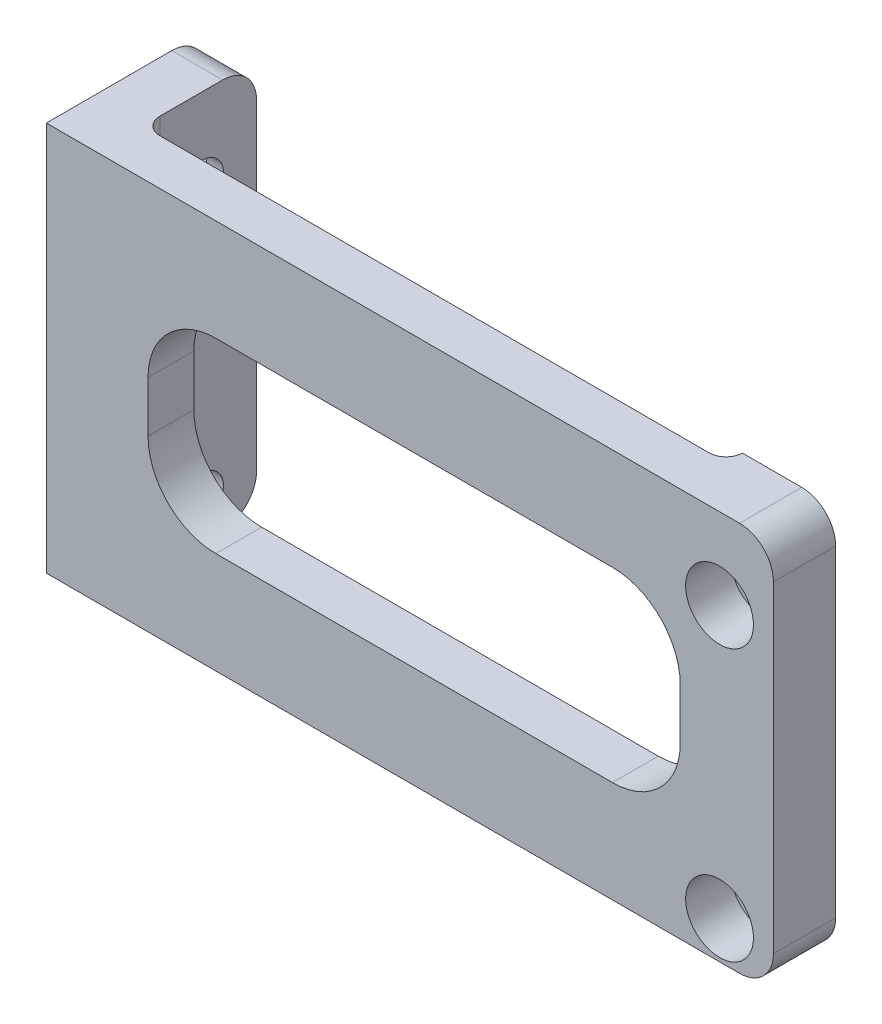
SolidWorks part; units mm, degrees
ref_plane "Front Plane" through (0, 0, 0) normal (0, 0, 1) x (1, 0, 0)
ref_plane "Top Plane" through (0, 0, 0) normal (0, 1, 0) x (1, 0, 0)
ref_plane "Right Plane" through (0, 0, 0) normal (1, 0, 0) x (0, 0, -1)
sketch "Sketch1" plane through (0, 0, 0) normal (0, 0, 1) x (1, 0, 0)
  line L0 (-15.45, 11.5) -> (-15.45, 5.5) construction
  line L1 (21.45, 11.5) -> (-21.45, 11.5)
  line L2 (21.45, 11.5) -> (21.45, -11.5)
  line L3 (21.45, -11.5) -> (-21.45, -11.5)
  line L4 (-21.45, 11.5) -> (-21.45, -11.5)
  line L5 (21.45, 11.5) -> (-21.45, -11.5) construction
  line L6 (21.45, -11.5) -> (-21.45, 11.5) construction
  line L7 (-21.45, 11.5) -> (-18.45, 11.5)
  line L8 (-21.45, 11.5) -> (-21.45, -11.5)
  line L9 (-21.45, -11.5) -> (-18.45, -11.5)
  line L10 (-18.45, 11.5) -> (-18.45, -11.5)
  line L11 (21.45, 11.5) -> (15.95, 11.5)
  line L12 (21.45, 11.5) -> (21.45, -11.5)
  line L13 (21.45, -11.5) -> (15.95, -11.5)
  line L14 (15.95, 11.5) -> (15.95, -11.5)
  line L15 (-15.45, 5.5) -> (15.95, 5.5)
  line L16 (-15.45, 5.5) -> (-15.45, -5.5)
  line L17 (-15.45, -5.5) -> (15.95, -5.5)
  line L18 (15.95, 5.5) -> (15.95, -5.5)
  line L19 (-15.45, 5.5) -> (-21.45, 5.5) construction
  line L20 (-15.45, -5.5) -> (-15.45, -11.5) construction
  circle A0 centre (18.27, -9.28) radius 1.1
  circle A1 centre (18.27, 6.72) radius 1.1
  point P0 (0, 0)
  dimension "D1" = 2.2
  dimension "D2" = 4.78
  dimension "D3" = 23
  dimension "D4" = 2.22
  dimension "D5" = 5.5
  dimension "D6" = 2.32
  dimension "D7" = 42.9
  dimension "D8" = 3
  dimension "D9" = 11
extrude "Boss-Extrude1" add sketch "Sketch1" against normal blind 2.7 contours L14 L1 L10 L3 region at (15.5362, 8.5, 0)
extrude "Boss-Extrude2" add sketch "Sketch1<3>" against normal blind 3.67 contours L1 L14 L3 L2 A1 A0 region at (18.7275, 0.0818, 0)
sketch "Sketch1<3>" plane through (0, 0, 0) normal (0, 0, 1) x (1, 0, 0) same geometry as "Sketch1"
extrude "Boss-Extrude3" add sketch "Sketch1<4>" against normal blind 9.4 contours L10 L1 L4 L3 region at (-19.95, 0, 0)
sketch "Sketch1<4>" plane through (0, 0, 0) normal (0, 0, 1) x (1, 0, 0) same geometry as "Sketch1"
sketch "Sketch2" plane through (-21.45, 0, 0) normal (-1, 0, 0) x (0, 0, 1)
  line L0 (-9.4, 11.5) -> (0, 11.5) construction
  line L1 (0, 11.5) -> (0, -11.5) construction
  circle A0 centre (-6.2, 6.75) radius 1.25
  dimension "D1" = 2.5
  dimension "D2" = 4.75
  dimension "D3" = 6.2
extrude "Cut-Extrude1" cut sketch "Sketch2" against normal up to surface (3 mm away) up to face at (-18.45, 0, -4.7)
pattern_linear "LPattern1" count 2 spacing 16 along (0, -1, 0) of "Cut-Extrude1"
sketch "Sketch3" plane through (-21.45, 0, 0) normal (-1, 0, 0) x (0, 0, 1)
  circle A0 centre (-6.2, 6.75) radius 2
  circle A1 centre (-6.2, -9.25) radius 2
  dimension "D1" = 4
extrude "Cut-Extrude2" cut sketch "Sketch3" against normal offset from surface (2 mm away) 1 up to face at (-18.45, -10.5, -6.2)
sketch "Sketch4" plane through (0, 0, 0) normal (0, 0, 1) x (1, 0, 0)
  circle A0 centre (18.27, 6.72) radius 2
  circle A1 centre (18.27, -9.28) radius 2
  dimension "D1" = 4
extrude "Cut-Extrude3" cut sketch "Sketch4" against normal offset from surface (2.67 mm away) 1 up to face at (19.37, 6.72, -3.67)
combine bodies "Combine1" operation type add bodies to combine 106 107
fillet "Fillet1" radius 2 4 edges at (21.45, -11.5, -1.835) (21.45, 11.5, -1.835) (-19.95, -11.5, -9.4) (-19.95, 11.5, -9.4)
fillet "Fillet2" radius 1 3 edges at (-18.45, 0, -2.7) (15.95, -8.5, -2.7) (15.95, 8.5, -2.7)
fillet "Fillet3" radius 4 4 edges at (15.95, -5.5, -1.835) (15.95, 5.5, -1.835) (-15.45, 5.5, -1.35) (-15.45, -5.5, -1.35)
